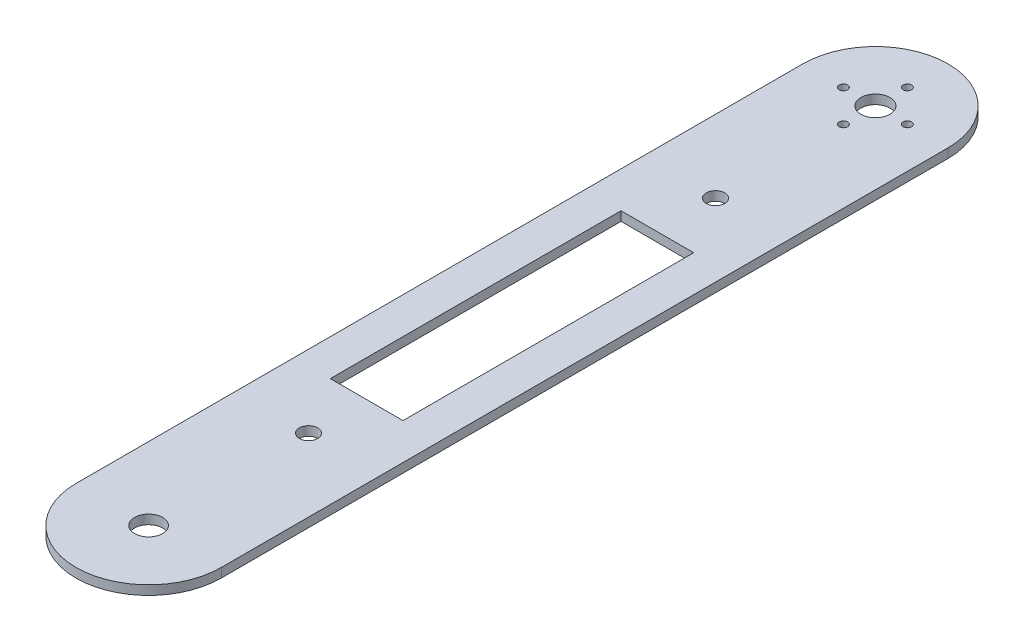
SolidWorks part; units mm, degrees
ref_plane "Front" through (0, 0, 0) normal (0, 0, 1) x (1, 0, 0)
ref_plane "Top" through (0, 0, 0) normal (0, 1, 0) x (1, 0, 0)
ref_plane "Right" through (0, 0, 0) normal (1, 0, 0) x (0, 0, -1)
sketch "Sketch1" plane through (0, 0, 0) normal (0, 1, 0) x (1, 0, 0)
  line L0 (25, 150) -> (-25, -150) construction
  line L1 (-25, 150) -> (25, 150)
  line L2 (-25, 150) -> (-25, -150)
  line L3 (-25, -150) -> (25, -150)
  line L4 (25, 150) -> (25, -150)
  line L5 (-25, 150) -> (25, -150) construction
  dimension "D1" = 300
  dimension "D2" = 50
extrude "Boss-Extrude1" add sketch "Sketch1" along normal mid plane 3.175
sketch "Sketch2" plane through (0, 1.5875, 0) normal (0, 1, 0) x (1, 0, 0)
  line L0 (-25, 125) -> (-25, 150)
  line L1 (-25, 150) -> (25, 150)
  line L2 (25, 150) -> (25, 125)
  line L3 (-25, -125) -> (-25, -150)
  line L4 (-25, -150) -> (25, -150)
  line L5 (25, -150) -> (25, -125)
  circle A0 centre (0, 125) radius 25
  circle A1 centre (0, -125) radius 25
  line M1 (-25, 150) -> (-25, -150)
  line M2 (-25, -150) -> (25, -150)
  line M3 (25, -150) -> (25, 150)
  line M4 (25, 150) -> (-25, 150)
extrude "Cut-Extrude1" cut sketch "Sketch2" against normal blind 6.35 contours A0 M3 M4 | A0 L1 M1 | A1 L4 M3 | A1 M1 M2 region at (-19.4158, 1.5875, -144.4158) region at (19.4158, 1.5875, -144.4158) region at (-19.4158, 1.5875, 144.4158) region at (19.4158, 1.5875, 144.4158)
sketch "Sketch3" plane through (0, 1.5875, 0) normal (0, 1, 0) x (1, 0, 0)
  line L0 (0, 150) -> (0, -150) construction
  line L1 (-25, 125) -> (25, 125) construction
  arc A0 (25, 125) -> (-25, 125) centre (0, 125) ccw construction
  circle A1 centre (0, 125) radius 5
  circle A2 centre (0, -125) radius 4.82
  arc A7 (-25, -125) -> (25, -125) centre (0, -125) ccw construction
  dimension "D2" = 9.64
  dimension "D3" = 10
extrude "Cut-Extrude2" cut sketch "Sketch3" against normal blind 6.35
sketch "Sketch4" plane through (0, 1.5875, 0) normal (0, 1, 0) x (1, 0, 0)
  line L0 (0, 150) -> (0, -150) construction
  line L1 (-25, 0) -> (25, 0) construction
  line L2 (-12.5, 50) -> (12.5, 50)
  line L3 (-12.5, 50) -> (-12.5, -50)
  line L4 (-12.5, -50) -> (12.5, -50)
  line L5 (12.5, 50) -> (12.5, -50)
  line L6 (-25, 125) -> (-25, -125) construction
  line L7 (25, -125) -> (25, 125) construction
  circle A0 centre (0, 70) radius 3.175
  circle A1 centre (0, -70) radius 3.175
  arc A2 (25, 125) -> (-25, 125) centre (0, 125) ccw construction
  arc A3 (-25, -125) -> (25, -125) centre (0, -125) ccw construction
  dimension "D3" = 6.35
  dimension "D4" = 70
  dimension "D1" = 25
  dimension "D2" = 100
extrude "Cut-Extrude3" cut sketch "Sketch4" against normal blind 6.35
hole_wizard "M2.5 Clearance Hole1" positions "Sketch7" profile "Sketch5" hole size "M2.5" standard "ANSI Metric" end condition up to next
sketch "Sketch7" plane through (0, 1.5875, 0) normal (0, 1, 0) x (1, 0, 0)
  circle A0 centre (0, 125) radius 11 construction
  point P7 (11, 125)
  point P9 (0, 136)
  point P11 (-11, 125)
  point P13 (0, 114)
  dimension "D1" = 22
sketch "Sketch5" plane through (11, 1.5875, -125) normal (1, 0, 0) x (0, 0, 1)
  line L0 (0, 0) -> (0, 3.175)
  line L1 (0, 3.175) -> (1.45, 3.175)
  line L2 (1.45, 3.175) -> (1.45, 0)
  line L5 (1.45, 0) -> (0, 0)
  line L11 (0, -6.35) -> (0, 107.95) construction
  dimension "Thru Hole Dia." = 2.9
  dimension "Thru Hole Depth" = 3.175
